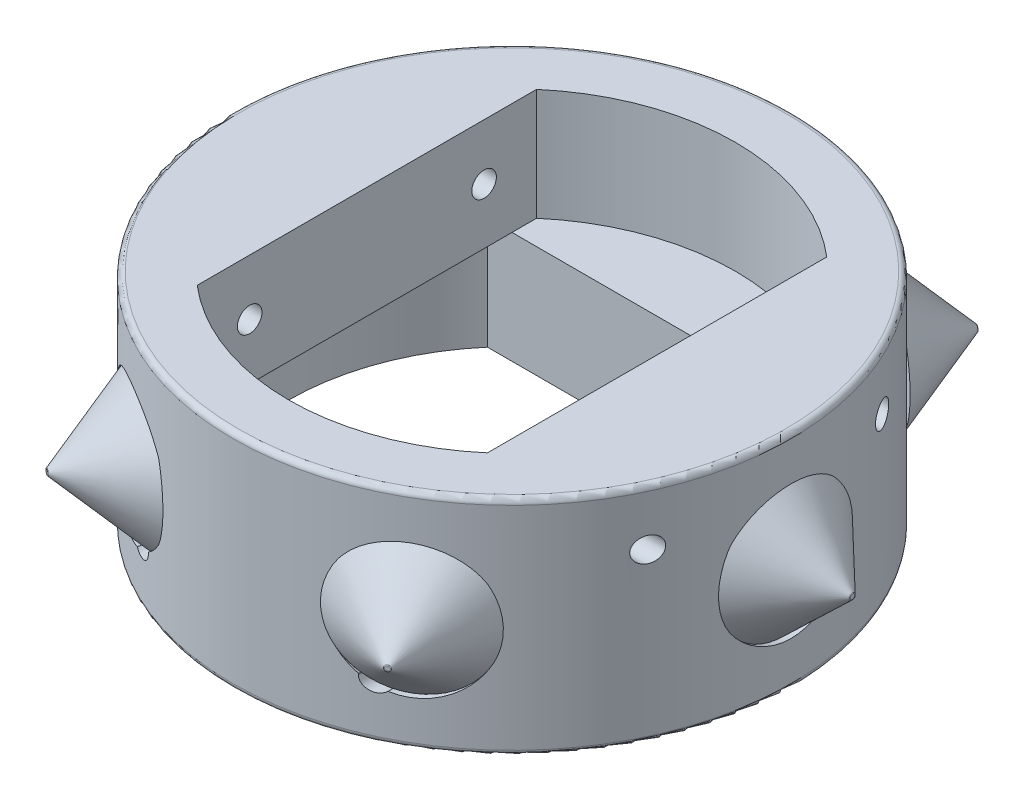
SolidWorks part; units mm, degrees
material "ABS"
ref_plane "正面" through (0, 0, 0) normal (0, 0, 1) x (1, 0, 0)
ref_plane "平面" through (0, 0, 0) normal (0, 1, 0) x (1, 0, 0)
ref_plane "右側面" through (0, 0, 0) normal (1, 0, 0) x (0, 0, -1)
sketch "ｽｹｯﾁ1" plane through (0, 0, 0) normal (0, 1, 0) x (1, 0, 0)
  circle A0 centre (0, 0) radius 25
  circle A1 centre (0, 0) radius 20
  dimension "D1" = 40
  dimension "D2" = 50
extrude "ﾎﾞｽ - 押し出し1" add sketch "ｽｹｯﾁ1" along normal blind 10 and the other way blind 10
fillet "ﾌｨﾚｯﾄ1" radius 0.5 2 edges at (0, -10, 25) (0, 10, 25)
sketch "ｽｹｯﾁ2" plane through (0, 0, 0) normal (0, 0, 1) x (1, 0, 0)
  line L0 (30.4692, 0.2795) -> (24.5, 6)
  line L1 (24.5, 6) -> (24.5, 0)
  line L2 (24.5, 0) -> (30.5, 0) construction
  line L4 (-25, 9.5) -> (25, 9.5) construction
  line L5 (-25, 9.5) -> (25, 9.5) construction
  line L6 (30.5, 0) -> (24.5, 0)
  line L7 (30.5, 0) -> (30.5, 0.2073)
  arc A0 (30.5, 0.2073) -> (30.4692, 0.2795) centre (30.4, 0.2073) ccw
  point P4 (30.5, 0.25)
  dimension "D5" = 0.1
  dimension "D1" = 0.5
  dimension "D2" = 6
  dimension "D3" = 6
  dimension "D4" = 0.25
revolve "回転1" add sketch "ｽｹｯﾁ2" angle 360 about L6 region at (26.58, 2.0034, 0) other way angle 360
ref_axis "軸1" through (0, -10, 0) along (0, 1, 0)
pattern_circular "円形ﾊﾟﾀｰﾝ5" count 6 over 360 about axis through (0, -10, 0) along (0, 1, 0) of bodies 102
sketch "ｽｹｯﾁ3" plane through (-12.25, 0, 21.2176) normal (0.5, 0, -0.866) x (-0.866, 0, -0.5)
  circle A0 centre (0, 0) radius 4.25
  dimension "D1" = 8.5
extrude "ｶｯﾄ - 押し出し1" cut sketch "ｽｹｯﾁ3" against normal blind 10
pattern_circular "円形ﾊﾟﾀｰﾝ6" count 6 over 360 about axis through (0, -10, 0) along (0, 1, 0) of "ｶｯﾄ - 押し出し1"
sketch "ｽｹｯﾁ4" plane through (0, 0, 0) normal (0, -1, 0) x (1, 0, 0)
  line L0 (-13, 15.1987) -> (-13, -15.1987)
  line L1 (13, 15.1987) -> (13, -15.1987)
  arc A1 (-13, 15.1987) -> (-13, -15.1987) centre (0, 0) ccw
  arc A2 (13, -15.1987) -> (13, 15.1987) centre (0, 0) ccw
  circle A3 centre (0, 0) radius 20 construction
  dimension "D1" = 13
  dimension "D2" = 13
extrude "ﾎﾞｽ - 押し出し2" add sketch "ｽｹｯﾁ4" against normal up to surface (10 mm away) up to face at (0, 10, 24.5)
sketch "ｽｹｯﾁ5" plane through (13, 0, 0) normal (-1, 0, 0) x (0, 0, 1)
  line L0 (15.1987, 5) -> (-15.1987, 5) construction
  line L1 (24.5, 10) -> (-24.5, 10) construction
  line L3 (0, -11) -> (0, 11) construction
  circle A0 centre (10.5, 5) radius 1.1
  circle A1 centre (-10.5, 5) radius 1.1
  dimension "D1" = 2.2
  dimension "D2" = 10.5
  dimension "D3" = 10.5
  dimension "D4" = 5
extrude "ｶｯﾄ - 押し出し2" cut sketch "ｽｹｯﾁ5" against normal through all both and the other way through all
sketch "ｽｹｯﾁ7" plane through (0, 0, 0) normal (0, -1, 0) x (1, 0, 0)
  line L0 (15.1987, -13) -> (-15.1987, -13)
  line L3 (11, 0) -> (-11, 0) construction
  line L4 (15.1987, 13) -> (-15.1987, 13)
  circle A5 centre (0, 0) radius 20 construction
  arc A6 (15.1987, 13) -> (-15.1987, 13) centre (0, 0) ccw
  arc A7 (-15.1987, -13) -> (15.1987, -13) centre (0, 0) ccw
  dimension "D1" = 13
extrude "ﾎﾞｽ - 押し出し7" add sketch "ｽｹｯﾁ7" along normal up to surface (10 mm away) up to face at (0, -10, 24.5)
sketch "ｽｹｯﾁ8" plane through (0, 0, 13) normal (0, 0, -1) x (-1, 0, 0)
  line L0 (0, 0) -> (0, -10) construction
  line L1 (13, 0) -> (-13, 0) construction
  line L2 (-15.1987, -10) -> (15.1987, -10) construction
  line L3 (-15.1987, -5) -> (15.1987, -5) construction
  line L4 (-15.1987, -10) -> (-15.1987, 0) construction
  line L5 (15.1987, -10) -> (15.1987, 0) construction
  circle A1 centre (10.5, -5) radius 1.1
  circle A2 centre (-10.5, -5) radius 1.1
  dimension "D1" = 2.2
  dimension "D2" = 10.5
extrude "ｶｯﾄ - 押し出し3" cut sketch "ｽｹｯﾁ8" against normal through all
sketch "ｽｹｯﾁ9" plane through (-24.5, 0, 0) normal (1, 0, 0) x (0, 0, -1)
  circle A0 centre (0, 0) radius 6 construction
  circle A1 centre (0, 0) radius 6
extrude "ｶｯﾄ - 押し出し4" cut sketch "ｽｹｯﾁ9" against normal through all
pattern_circular "円形ﾊﾟﾀｰﾝ7" count 6 over 360 about axis through (0, -10, 0) along (0, 1, 0) of "ｶｯﾄ - 押し出し4"
